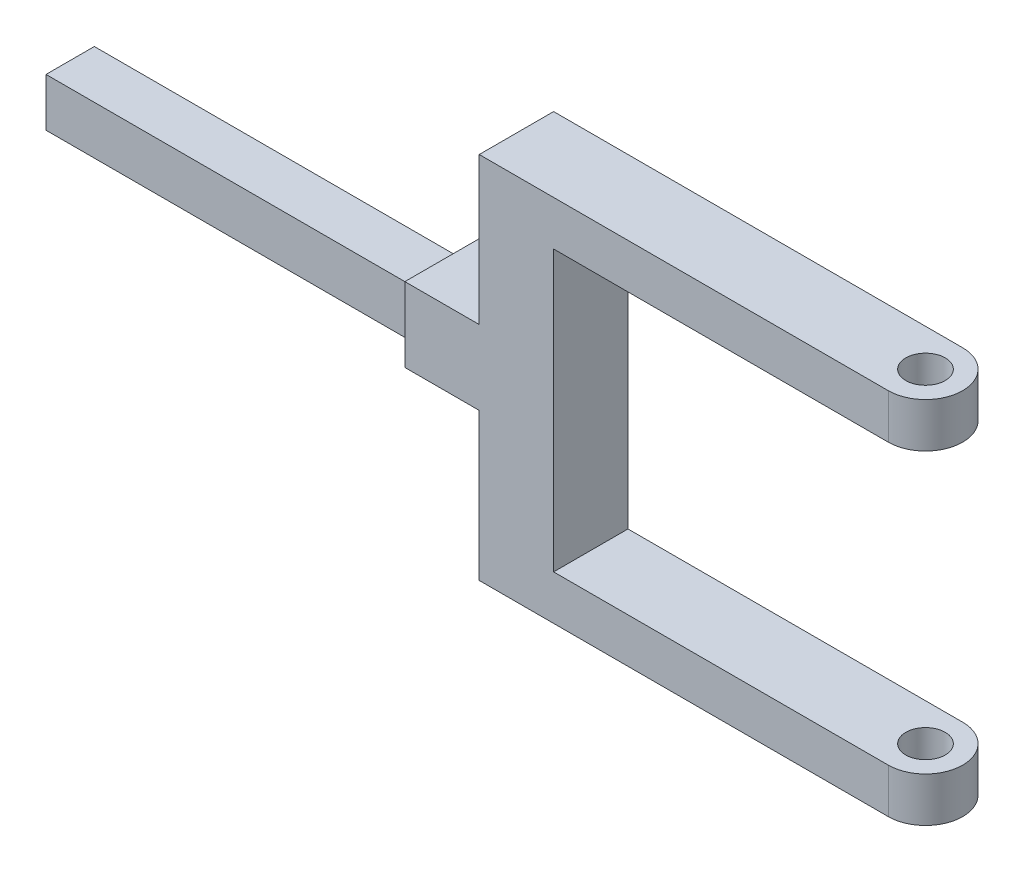
SolidWorks part; units mm, degrees
ref_plane "前视基准面" through (0, 0, 0) normal (0, 0, 1) x (1, 0, 0)
ref_plane "上视基准面" through (0, 0, 0) normal (0, 1, 0) x (1, 0, 0)
ref_plane "右视基准面" through (0, 0, 0) normal (1, 0, 0) x (0, 0, -1)
other "Configuration Table"
sketch "草图1" plane through (0, 0, 0) normal (0, 0, 1) x (1, 0, 0)
  line L0 (0, 18.8) -> (0, -18.8)
  line L1 (0, 18.8) -> (50, 18.8)
  line L2 (50, 18.8) -> (50, 24.8)
  line L3 (50, 24.8) -> (-10, 24.8)
  line L4 (-10, 24.8) -> (-10, -24.8)
  line L5 (-10, -24.8) -> (50, -24.8)
  line L6 (50, -24.8) -> (50, -18.8)
  line L7 (50, -18.8) -> (0, -18.8)
  point P4 (0, 0)
  dimension "D1" = 37.6
  dimension "D2" = 50
  dimension "D3" = 6
  dimension "D4" = 10
extrude "凸台-拉伸1" add sketch "草图1" along normal blind 10
sketch "草图2" plane through (-10, 0, 0) normal (-1, 0, 0) x (0, 0, 1)
  line L0 (8.25, 3.25) -> (8.25, -3.25)
  line L1 (1.75, -3.25) -> (8.25, -3.25)
  line L2 (1.75, 3.25) -> (1.75, -3.25)
  line L3 (1.75, 3.25) -> (8.25, 3.25)
  line L4 (5, 24.8) -> (5, -24.8) construction
  line L5 (0, 0) -> (10, 0) construction
  line L7 (0, 5) -> (10, 5)
  line L8 (0, 24.8) -> (0, -24.8)
  line L9 (0, -24.8) -> (10, -24.8)
  line L10 (10, -24.8) -> (10, 24.8)
  line L11 (10, 24.8) -> (0, 24.8)
  line L12 (0, 24.8) -> (0, -24.8)
  line L13 (0, -24.8) -> (10, -24.8)
  line L14 (10, -24.8) -> (10, 24.8)
  line L15 (10, 24.8) -> (0, 24.8)
  line L16 (0, 5) -> (0, -5)
  line L17 (0, -5) -> (10, -5)
  line L18 (10, 5) -> (10, -5)
  line L19 (5, -5) -> (5, 5) construction
  line L20 (0, 0) -> (10, 0) construction
  line L21 (1.5, 3.5) -> (8.5, 3.5) construction
  line L22 (1.5, 3.5) -> (1.5, -3.5) construction
  line L23 (1.5, -3.5) -> (8.5, -3.5) construction
  line L24 (8.5, 3.5) -> (8.5, -3.5) construction
  line L25 (5, -3.5) -> (5, 3.5) construction
  line L26 (1.5, 0) -> (8.5, 0) construction
  point P6 (5, 0)
  point P13 (5, 0)
  line M8 (0, 24.8) -> (0, -24.8)
  dimension "D2" = 10
  dimension "D3" = 1.5
  dimension "D4" = 0.25
  dimension "D1" = 0
extrude "凸台-拉伸2" add sketch "草图2" along normal blind 10 contours L17 L14 L7 L2 L3 L0 L1 M8 | L3 L2 L1 L0 region at (-10, 0, 5) region at (-10, 4.8586, 5)
extrude "凸台-拉伸3" add sketch "草图2<3>" along normal blind 50 from surface contours L3 L2 L1 L0 region at (-10, 0, 5) starting at face at (-20, 0, 5)
sketch "草图2<3>" plane through (-10, 0, 0) normal (-1, 0, 0) x (0, 0, 1) same geometry as "草图2"
sketch "草图3" plane through (0, 24.8, 0) normal (0, 1, 0) x (1, 0, 0)
  line L0 (-10, -5) -> (50, -5) construction
  line L1 (-10, 0) -> (-10, -10) construction
  line L2 (50, -10) -> (50, 0) construction
  line L3 (50, 0) -> (-10, 0) construction
  circle A0 centre (45, -5) radius 5
  circle A1 centre (45, -5) radius 2.65
  line M1 (50, 0) -> (-10, 0)
  line M3 (-10, -10) -> (50, -10)
  line M4 (50, -10) -> (50, 0)
  dimension "D1" = 5.3
extrude "切除-拉伸1" cut sketch "草图3" against normal through all contours A1 L0 | L0 A1 | A0 M4 M1 | A0 M3 M4 region at (45, 24.8, 6.1247) region at (45, 24.8, 3.8753) region at (48.8832, 24.8, 8.8832) region at (48.8832, 24.8, 1.1168)
